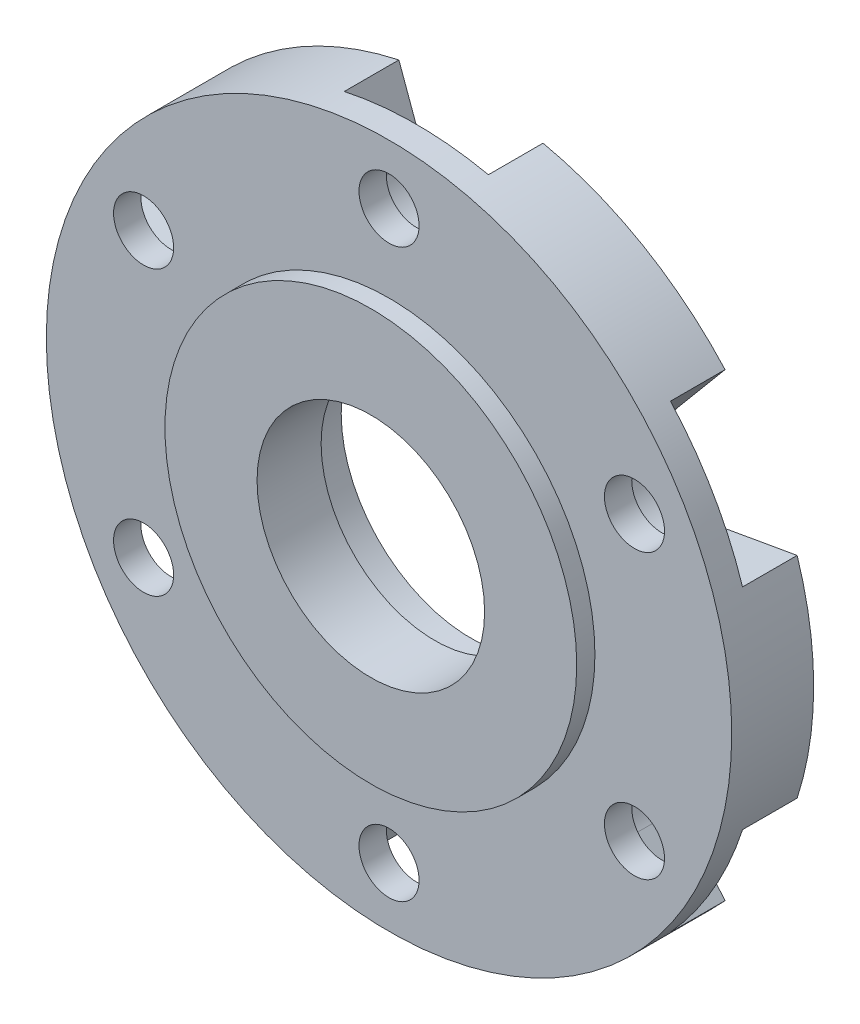
SolidWorks part; units mm, degrees
material "6061-T6 (SS)"
ref_plane "Front Plane" through (0, 0, 0) normal (0, 0, 1) x (1, 0, 0)
ref_plane "Top Plane" through (0, 0, 0) normal (0, 1, 0) x (1, 0, 0)
ref_plane "Right Plane" through (0, 0, 0) normal (1, 0, 0) x (0, 0, -1)
sketch "Sketch Spindle Skeleton" plane through (0, 0, 0) normal (1, 0, 0) x (0, 0, -1)
  line L0 (-119.6, -9.5) -> (-164, -9.5)
  line L5 (-1000, 0) -> (49000, 0)
  line L6 (0, -9.5) -> (0, 9.5)
  line L13 (0, 9.5) -> (-46.4, 9.5)
  line L26 (-46.4, 9.5) -> (-46.4, 14)
  line L27 (-46.4, 14) -> (-119.6, 14)
  line L32 (-119.6, 14) -> (-119.6, 9.5)
  line L34 (-180, 7) -> (-180, -7)
  line L36 (-119.6, -9.5) -> (-119.6, -14)
  line L37 (-119.6, -14) -> (-46.4, -14)
  line L38 (-46.4, -14) -> (-46.4, -9.5)
  line L39 (0, -9.5) -> (-46.4, -9.5)
  line L40 (-24.625, 37.6491) -> (-15.625, 37.6491)
  line L41 (-136.2, 22.6187) -> (-119.6, 22.6187)
  line L42 (-136.2, 22.6187) -> (-136.2, -22.6187)
  line L43 (-136.2, -22.6187) -> (-119.6, -22.6187)
  line L44 (-119.6, 22.6187) -> (-119.6, -22.6187)
  line L45 (-136.2, 22.6187) -> (-119.6, -22.6187) construction
  line L46 (-136.2, -22.6187) -> (-119.6, 22.6187) construction
  line L47 (-29.8, 22.6187) -> (-46.4, 22.6187)
  line L48 (-29.8, 22.6187) -> (-29.8, -22.6187)
  line L49 (-29.8, -22.6187) -> (-46.4, -22.6187)
  line L50 (-46.4, 22.6187) -> (-46.4, -22.6187)
  line L51 (-29.8, 22.6187) -> (-46.4, -22.6187) construction
  line L52 (-29.8, -22.6187) -> (-46.4, 22.6187) construction
  line L59 (-15.625, 37.6491) -> (-15.625, -37.6491)
  line L60 (-15.625, -37.6491) -> (-24.625, -37.6491)
  line L61 (-24.625, -22.6187) -> (-26.625, -22.6187)
  line L62 (-26.625, -22.6187) -> (-26.625, -12.5)
  line L63 (-26.625, -12.5) -> (-24.625, -12.5)
  line L64 (-24.625, -12.5) -> (-24.625, 12.5)
  line L65 (-24.625, 12.5) -> (-26.625, 12.5)
  line L66 (-26.625, 12.5) -> (-26.625, 22.6187)
  line L67 (-26.625, 22.6187) -> (-24.625, 22.6187)
  line L68 (-24.625, 22.6187) -> (-24.625, 37.6491)
  line L69 (-24.625, -22.6187) -> (-24.625, -37.6491)
  line L71 (-147.884, 37.6491) -> (-25.625, 37.6491)
  line L72 (-147.884, 37.6491) -> (-147.884, -37.6491)
  line L73 (-147.884, -37.6491) -> (-25.625, -37.6491)
  line L74 (-25.625, 37.6491) -> (-25.625, -37.6491)
  line L75 (-147.884, 37.6491) -> (-25.625, -37.6491) construction
  line L76 (-147.884, -37.6491) -> (-25.625, 37.6491) construction
  line L77 (-164, -9.5) -> (-164, -7)
  line L78 (-164, -7) -> (-180, -7)
  line L79 (-119.6, 9.5) -> (-164, 9.5)
  line L80 (-164, 7) -> (-180, 7)
  line L81 (-164, 9.5) -> (-164, 7)
  line L82 (-141.8, 9.5) -> (-141.8, -9.5) construction
  line L83 (-23.2, 9.5) -> (-23.2, -9.5) construction
  line L96 (-147.884, 37.6492) -> (-156.884, 37.6492)
  line L98 (-147.884, -37.6491) -> (-156.884, -37.6491)
  line L99 (-156.884, 37.6492) -> (-156.884, -37.6491)
  line L110 (-147.884, 37.6492) -> (-147.884, -37.6491)
  point P3 (0, 0)
  point P18 (-127.9, 0)
  point P24 (-38.1, 0)
  point P29 (-86.7545, 0)
  point P48 (-15.625, 31.1339)
  point P70 (-156.884, 31.1339)
revolve "Main Revolve" add sketch "Sketch Spindle Skeleton" angle 360 about L5 region at (0, 23.3435, 20.317) region at (0, 17.5594, 26.125)
sketch "Sketch Center Cut" plane through (0, 0, 24.625) normal (0, 0, 1) x (1, 0, 0)
  circle A3 centre (0, 0) radius 12.5
  dimension "D1" = 25
extrude "Cut Center" cut sketch "Sketch Center Cut" against normal through all both and the other way through all
hole_wizard "CBORE for M6 SHCS1" positions "Hole wizard sketch 1" profile "Hole wizard sketch 2" counterbore size "M6" standard "ANSI Metric" end condition through all
sketch "Hole wizard sketch 1" plane through (0, 0, 15.625) normal (0, 0, -1) x (-1, 0, 0)
  point P0 (0, 31.1339)
sketch "Hole wizard sketch 2" plane through (0, 31.1339, 15.625) normal (1, 0, 0) x (0, 1, 0)
  line L0 (0, 0) -> (0, 11)
  line L1 (0, 11) -> (3.3, 11)
  line L3 (3.3, 11) -> (3.3, 6)
  line L4 (3.3, 6) -> (5.5, 6)
  line L5 (5.5, 6) -> (5.5, 0)
  line L7 (5.5, 0) -> (0, 0)
  line L11 (0, -6.35) -> (0, 107.95) construction
  dimension "Thru Hole Dia." = 6.6
  dimension "Thru Hole Depth" = 11
  dimension "C'Bore Dia." = 11
  dimension "C'Bore Depth" = 6
pattern_circular "CirPattern1" count 6 over 360 about axis through (0, 0, 15.625) along (0, 0, 1) of "CBORE for M6 SHCS1"
sketch "Sketch1" plane through (0, 0, 15.625) normal (0, 0, -1) x (-1, 0, 0)
  circle A0 centre (0, 0) radius 14.2558
  dimension "D1" = 28.5115
extrude "Cut-Extrude1" cut sketch "Sketch1" against normal blind 3.9624
sketch "Sketch2" plane through (0, 0, 15.625) normal (0, 0, -1) x (-1, 0, 0)
  line L0 (-5.1683, 29.2528) -> (-7.9179, 36.8071)
  line L1 (0, 31.1339) -> (0, 37.65) construction
  line L2 (5.1683, 29.2528) -> (7.9179, 36.8071)
  circle A0 centre (0, 31.1339) radius 5.5 construction
  circle A1 centre (0, 0) radius 37.6491 construction
  arc A2 (-5.1683, 29.2528) -> (5.1683, 29.2528) centre (0, 31.1339) ccw
  point P37 (0.065, 0.0375)
  circle M8 centre (0, 31.1339) radius 5.5
  circle M9 centre (0, 0) radius 37.6491
  dimension "D1" = 20
extrude "Cut-Extrude2" cut sketch "Sketch2" against normal up to surface (6 mm away) contours L1 L2 M8 M9 | L1 L0 M8 M9 region at (4.7304, 35.5149, 15.625) region at (-4.7304, 35.5149, 15.625) up to face at (23.6628, -15.567, 21.625)
pattern_circular "CirPattern2" count 6 over 360 about axis through (0, 0, 1000) along (0, 0, 1) of "Cut-Extrude2" reverse direction yes
